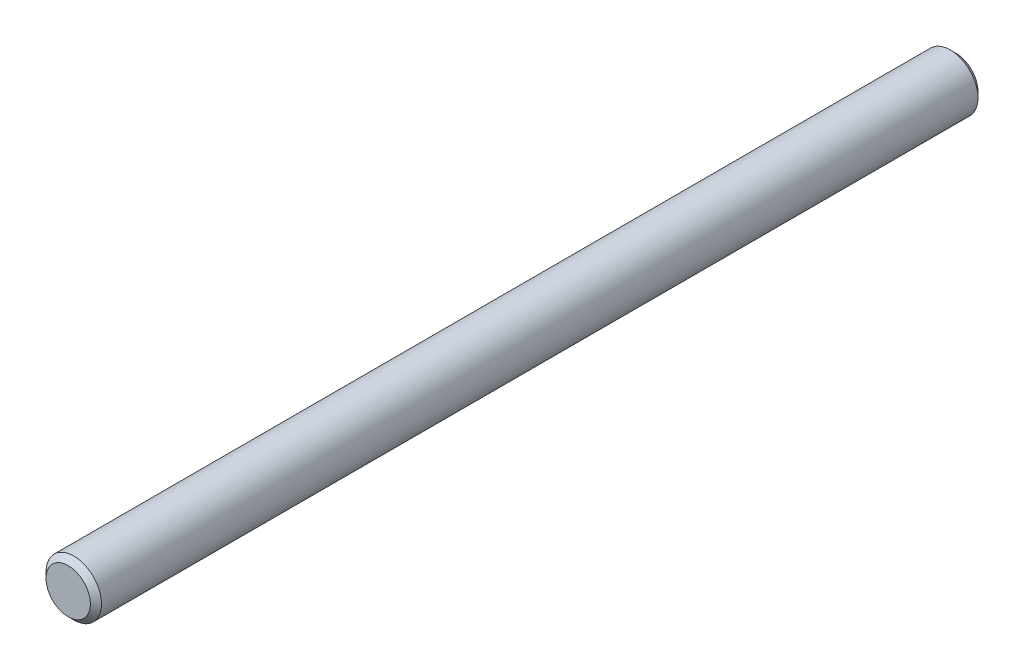
SolidWorks part; units mm, degrees
ref_plane "Front Plane" through (0, 0, 0) normal (0, 0, 1) x (1, 0, 0)
ref_plane "Top Plane" through (0, 0, 0) normal (0, 1, 0) x (1, 0, 0)
ref_plane "Right Plane" through (0, 0, 0) normal (1, 0, 0) x (0, 0, -1)
sketch "Sketch1" plane through (0, 0, 0) normal (0, 1, 0) x (1, 0, 0)
  line L0 (2, 20) -> (0, 20)
  line L1 (0, 20) -> (0, -60)
  line L2 (0, -60) -> (2, -60)
  line L3 (2, -60) -> (2.5, -59.5)
  line L4 (2.5, -59.5) -> (2.5, 19.5)
  line L5 (2.5, 19.5) -> (2, 20)
  line L6 (0, 20) -> (0, -60) construction
  dimension "D1" = 80
  dimension "D2" = 2.5
  dimension "D3" = 2
  dimension "D4" = 135
  dimension "D5" = 2
  dimension "D6" = 135
revolve "Revolve1" add sketch "Sketch1" angle 360 about L6 reverse direction yes
